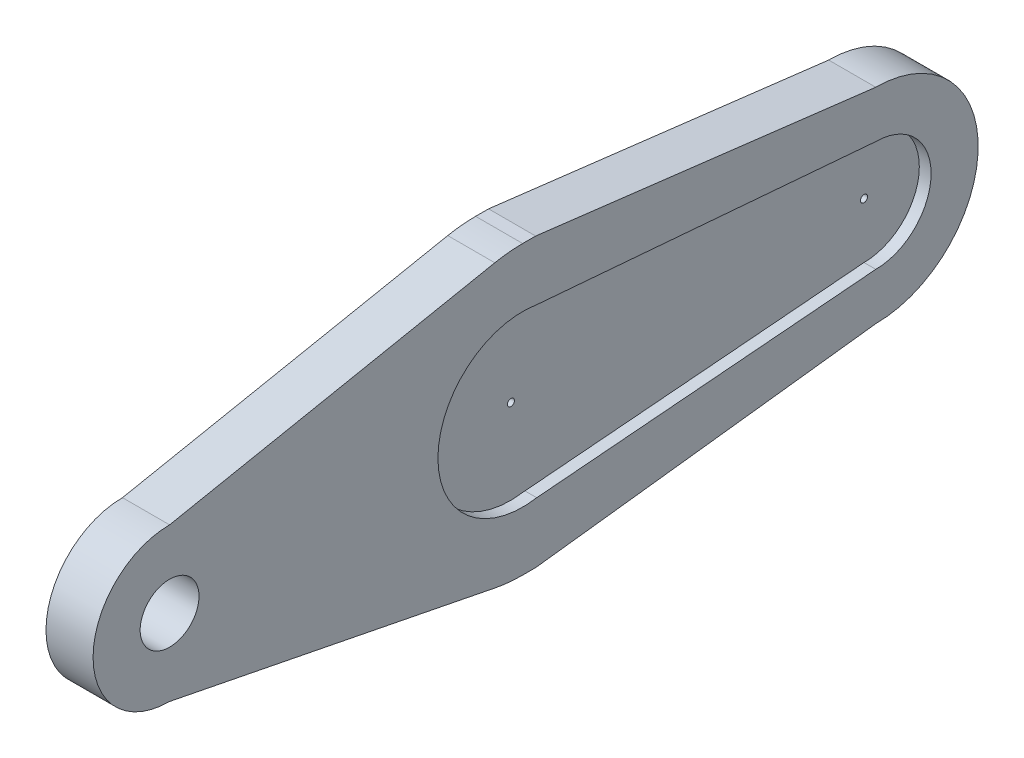
SolidWorks part; units mm, degrees
ref_plane "Front Plane" through (0, 0, 0) normal (1, 0, 0) x (0, 1, 0)
ref_plane "Top Plane" through (0, 0, 0) normal (0, 0, 1) x (0, 1, 0)
ref_plane "Right Plane" through (0, 0, 0) normal (0, 1, 0) x (-1, 0, 0)
sketch "Sketch2" plane through (0, 0, 0) normal (1, 0, 0) x (0, 1, 0)
  line L0 (0, -13.9832) -> (0, -33.5576) construction
  line L1 (-6.1, -18.8) -> (6.1, -18.8)
  line L2 (-6.1, -18.8) -> (-6.1, 18.8)
  line L3 (-6.1, 18.8) -> (6.1, 18.8)
  line L4 (6.1, -18.8) -> (6.1, 18.8)
  line L5 (-6.1, -18.8) -> (6.1, 18.8) construction
  line L6 (-6.1, 18.8) -> (6.1, -18.8) construction
  line L7 (2.35, -14.45) -> (3.6, 0.55)
  line L8 (-3.6, 0.55) -> (-2.35, -14.45)
  line L9 (-6.1, 0) -> (-4.35, -14.45)
  line L10 (4.35, -14.45) -> (6.1, 0)
  line L11 (-3.25, 15.55) -> (-5.984, 1.7341)
  line L12 (5.984, 1.7341) -> (3.25, 15.55)
  arc A1 (3.5503, -0.0459) -> (-3.5503, -0.0459) centre (0, 0.55) ccw
  arc A2 (-2.35, -14.45) -> (2.35, -14.45) centre (0, -14.45) ccw
  circle A3 centre (0, 15.55) radius 1.25
  arc A4 (3.25, 15.55) -> (-3.25, 15.55) centre (0, 15.55) ccw
  arc A5 (-4.35, -14.45) -> (4.35, -14.45) centre (0, -14.45) ccw
  arc A6 (-5.984, 1.7341) -> (-6.1, 0.55) centre (0, 0.55) ccw
  arc A7 (6.1, 0.55) -> (5.984, 1.7341) centre (0, 0.55) ccw
  point P0 (0, 0)
  dimension "D1" = 7.2
  dimension "D2" = 4.7
  dimension "D4" = 2.5
  dimension "D5" = 2
  dimension "D8" = 2
  dimension "D3" = 15
  dimension "D6" = 15
  dimension "D7" = 2.5
extrude "Boss-Extrude1" add sketch "Sketch2" along normal blind 2 contours L4 A7 L12 A4 L11 A6 L2 L9 A5 L10 A3 A2 L8 A1 L7 region at (0, -2.7964, -17.2464)
extrude "Boss-Extrude2" add sketch "Sketch2<3>" along normal blind 1.5 contours L8 A2 L7 A1 region at (0, 0, -5.6231)
sketch "Sketch2<3>" plane through (0, 0, 0) normal (1, 0, 0) x (0, 1, 0) same geometry as "Sketch2"
sketch "Sketch3" plane through (1.5, 0, 0) normal (1, 0, 0) x (0, 1, 0)
  circle A0 centre (0, 0.55) radius 0.15
  arc A1 (3.6, 0.55) -> (-3.6, 0.55) centre (0, 0.55) ccw construction
  circle A2 centre (0, -14.45) radius 0.15
  arc A3 (-2.35, -14.45) -> (2.35, -14.45) centre (0, -14.45) ccw construction
  dimension "D1" = 0.3
extrude "Cut-Extrude1" cut sketch "Sketch3" against normal blind 0.5
